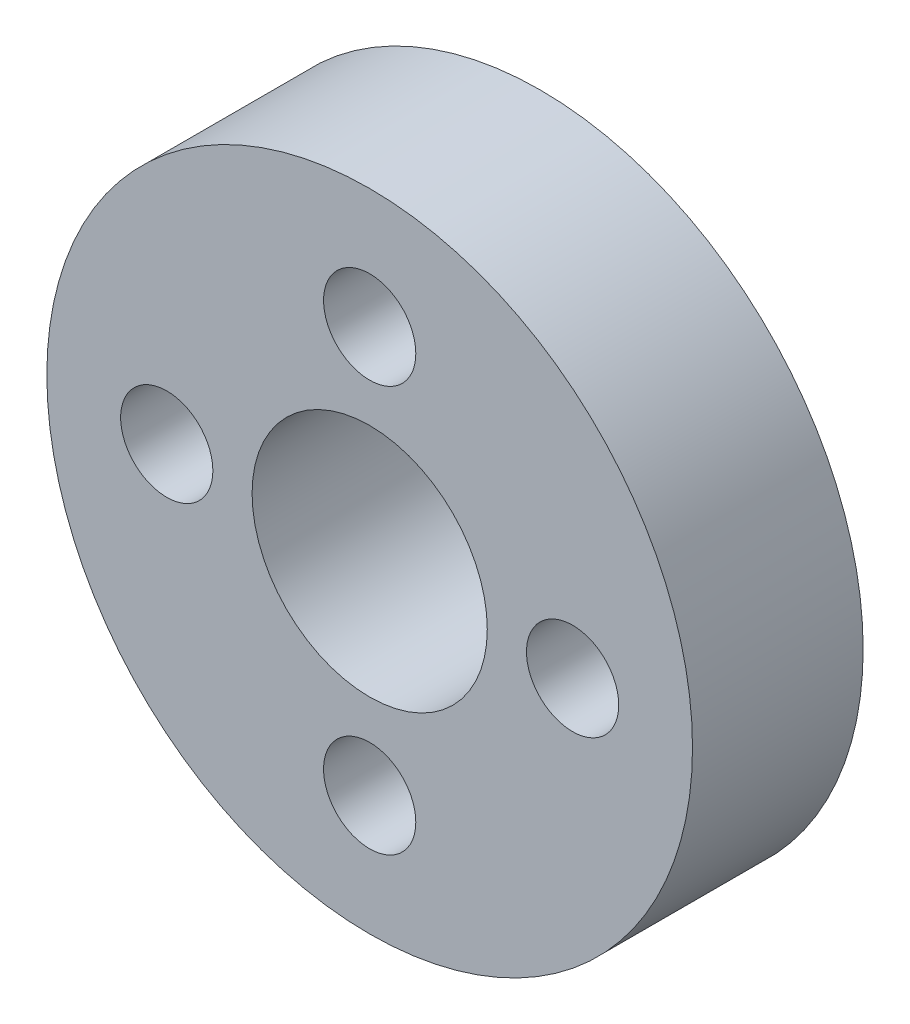
SolidWorks part; units mm, degrees
ref_plane "Front Plane" through (0, 0, 0) normal (0, 0, 1) x (1, 0, 0)
ref_plane "Top Plane" through (0, 0, 0) normal (0, 1, 0) x (1, 0, 0)
ref_plane "Right Plane" through (0, 0, 0) normal (1, 0, 0) x (0, 0, -1)
sketch "Sketch1" plane through (0, 0, 0) normal (0, 0, 1) x (1, 0, 0)
  line L0 (0, 11.176) -> (0, 0) construction
  line L5 (0, 0) -> (11.176, 0) construction
  line L6 (0, -11.176) -> (0, 0) construction
  line L7 (0, 0) -> (-11.176, 0) construction
  circle A0 centre (0, 0) radius 17.78
  circle A1 centre (-11.176, 0) radius 2.54
  circle A2 centre (0, -11.176) radius 2.54
  circle A3 centre (11.176, 0) radius 2.54
  circle A4 centre (0, 11.176) radius 2.54
  circle A5 centre (0, 0) radius 6.477
  dimension "D1" = 35.56
  dimension "D4" = 5.08
  dimension "D2" = 12.954
  dimension "D3" = 11.176
extrude "Boss-Extrude1" add sketch "Sketch1" along normal blind 9.398
sketch "Sketch2" plane through (0, 0, 0) normal (0, 0, -1) x (-1, 0, 0)
  line L1 (-8.255, -8.255) -> (8.255, -8.255)
  line L2 (-8.255, -8.255) -> (-8.255, 8.255)
  line L3 (-8.255, 8.255) -> (8.255, 8.255)
  line L4 (8.255, -8.255) -> (8.255, 8.255)
  line L5 (-8.255, -8.255) -> (8.255, 8.255) construction
  line L6 (-8.255, 8.255) -> (8.255, -8.255) construction
  circle A0 centre (0, 0) radius 6.477 construction
  circle A1 centre (0, 0) radius 6.477
  point P0 (0, 0)
  dimension "D1" = 16.51
extrude "Boss-Extrude2" add sketch "Sketch2" along normal blind 3.175
